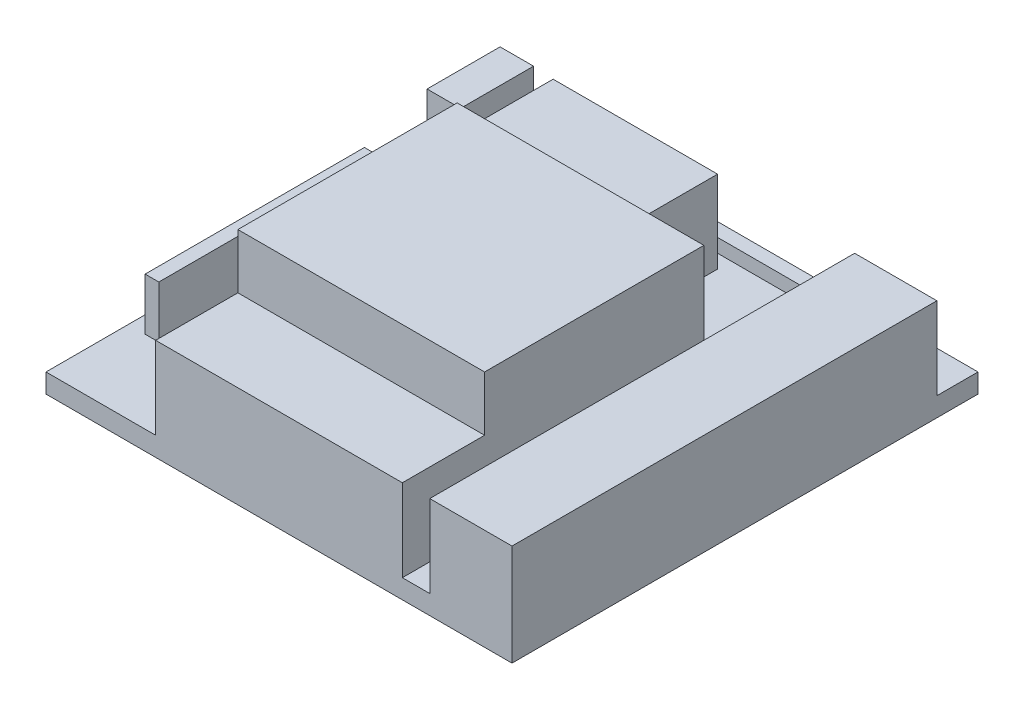
SolidWorks part; units mm, degrees
ref_plane "Front Plane" through (0, 0, 0) normal (0, 0, 1) x (1, 0, 0)
ref_plane "Top Plane" through (0, 0, 0) normal (0, 1, 0) x (1, 0, 0)
ref_plane "Right Plane" through (0, 0, 0) normal (1, 0, 0) x (0, 0, -1)
sketch "Sketch1" plane through (0, 0, 0) normal (0, 1, 0) x (1, 0, 0)
  line L1 (-85, -85) -> (85, -85)
  line L2 (-85, -85) -> (-85, 85)
  line L3 (-85, 85) -> (85, 85)
  line L4 (85, -85) -> (85, 85)
  line L5 (-85, -85) -> (85, 85) construction
  line L6 (-85, 85) -> (85, -85) construction
  point P0 (0, 0)
  dimension "D1" = 170
extrude "alusplaat" add sketch "Sketch1" along normal blind 2
sketch "Sketch2" plane through (0, 2, 0) normal (0, 1, 0) x (-1, 0, 0)
  line L1 (-85, 85) -> (-55, 85)
  line L2 (-85, 85) -> (-85, -70)
  line L3 (-85, -70) -> (-55, -70)
  line L4 (-55, 85) -> (-55, -70)
  dimension "D1" = 155
  dimension "D2" = 30
extrude "pistikud" add sketch "Sketch2" along normal blind 35
sketch "Sketch3" plane through (0, 2, 0) normal (0, 1, 0) x (1, 0, 0)
  line L0 (-85, -85) -> (55, -85) construction
  line L1 (-45, -85) -> (45, -85)
  line L2 (-45, -85) -> (-45, 25)
  line L3 (-45, 25) -> (45, 25)
  line L4 (45, -85) -> (45, 25)
  line L5 (-85, 85) -> (-85, -85) construction
  dimension "D1" = 90
  dimension "D2" = 40
  dimension "D3" = 110
extrude "cpu+mälud" add sketch "Sketch3" along normal blind 55
sketch "Sketch4" plane through (0, 2, 0) normal (0, 1, 0) x (1, 0, 0)
  line L1 (5, 35) -> (-55, 35)
  line L2 (5, 35) -> (5, 70)
  line L3 (5, 70) -> (-55, 70)
  line L4 (-55, 35) -> (-55, 70)
  line L5 (-85, 85) -> (-85, -85) construction
  line L6 (85, 85) -> (-85, 85) construction
  dimension "D1" = 35
  dimension "D2" = 60
  dimension "D3" = 30
  dimension "D4" = 15
extrude "sinine radikas" add sketch "Sketch4" along normal blind 35
sketch "Sketch5" plane through (0, 2, 0) normal (0, 1, 0) x (-1, 0, 0)
  line L0 (85, -85) -> (85, 85) construction
  line L1 (45, -75) -> (-45, -75)
  line L2 (45, -75) -> (45, -80)
  line L3 (45, -80) -> (-45, -80)
  line L4 (-45, -75) -> (-45, -80)
  line L5 (-85, -85) -> (85, -85) construction
  dimension "D1" = 90
  dimension "D2" = 40
  dimension "D3" = 5
  dimension "D4" = 5
extrude "pcie pesa" add sketch "Sketch5" along normal blind 10
sketch "Sketch6" plane through (0, 2, 0) normal (0, 1, 0) x (-1, 0, 0)
  line L1 (67.672, -48.9124) -> (79.8888, -48.9124)
  line L2 (67.672, -48.9124) -> (67.672, -75.5395)
  line L3 (67.672, -75.5395) -> (79.8888, -75.5395)
  line L4 (79.8888, -48.9124) -> (79.8888, -75.5395)
extrude "raid pesad" add sketch "Sketch6" along normal blind 30
sketch "Sketch7" plane through (0, 2, 0) normal (0, 1, 0) x (-1, 0, 0)
  line L1 (85, -85) -> (-85, -85)
  line L2 (85, -85) -> (85, 85)
  line L3 (85, 85) -> (-85, 85)
  line L4 (-85, -85) -> (-85, 85)
extrude "üleüldine müra" add sketch "Sketch7" along normal blind 5
sketch "Sketch8" plane through (0, 7, 0) normal (0, 1, 0) x (-1, 0, 0)
  line L0 (-85, -85) -> (85, -85) construction
  line L1 (78.8401, -25) -> (73.8401, -25)
  line L2 (78.8401, -25) -> (78.8401, 55)
  line L3 (78.8401, 55) -> (73.8401, 55)
  line L4 (73.8401, -25) -> (73.8401, 55)
  dimension "D1" = 5
  dimension "D2" = 80
  dimension "D3" = 60
extrude "patrei ja igasugused lülitid" add sketch "Sketch8" along normal blind 19
sketch "Sketch9" plane through (0, 57, 0) normal (0, 1, 0) x (-1, 0, 0)
  line L0 (-45, 85) -> (-45, -25) construction
  line L1 (45, -25) -> (-45, -25)
  line L2 (45, -25) -> (45, 55)
  line L3 (45, 55) -> (-45, 55)
  line L4 (-45, -25) -> (-45, 55)
  dimension "D1" = 80
extrude "Cut-Extrude1" cut sketch "Sketch9" against normal blind 20 flip side to cut
